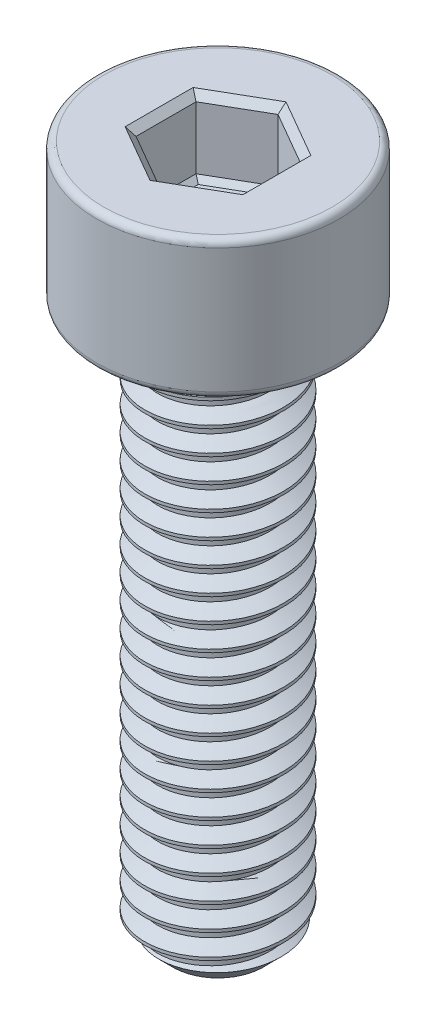
SolidWorks part; units mm, degrees
material "AISI Type A2 Tool Steel"
ref_plane "Front Plane" through (0, 0, 0) normal (0, 0, 1) x (1, 0, 0)
ref_plane "Top Plane" through (0, 0, 0) normal (0, 1, 0) x (1, 0, 0)
ref_plane "Right Plane" through (0, 0, 0) normal (1, 0, 0) x (0, 0, -1)
sketch "Sketch1" plane through (0, 0, 0) normal (0, 1, 0) x (1, 0, 0)
  circle A0 centre (0, 0) radius 2
  dimension "D1" = 4
extrude "Boss-Extrude1" add sketch "Sketch1" along normal blind 16
thread "Thread1" pitch 0.7 start angle 0, offset 1, length 0, pitch 0.7, diameter 4
ref_plane "Plane1" through (2, -1, 0) normal (0, 0, 1) x (1, 0, 0)
sketch "Thread Profile1" plane through (2, -1, 0) normal (0, 0, 1) x (1, 0, 0)
  line L0 (0, 0) -> (0, 0.7) construction
  line L11 (0, 0) -> (0, 0.6125)
  line L12 (0, 0.6125) -> (-0.3789, 0.3937)
  line L13 (-0.3789, 0.3937) -> (-0.3789, 0.2187)
  line L15 (-0.3789, 0.2187) -> (0, 0)
  line L17 (-0.3789, 0.3062) -> (0, 0.3062) construction
  point P2 (0, 0)
  dimension "Pitch" = 0.7
  dimension "Profile_Angle" = 60
  dimension "Profile_Land" = 0.175
  dimension "Profile_Height" = 0.3789
sketch "Sketch4" plane through (0, 16, 0) normal (0, -1, 0) x (-1, 0, 0)
  circle A0 centre (0, 0) radius 3.5
  dimension "D1" = 7
extrude "Boss-Extrude2" add sketch "Sketch4" against normal blind 4
fillet "Fillet1" radius 0.2 2 edges at (0, 16, -3.5) (0, 20, -3.5)
sketch "Sketch6" plane through (0, 0, 0) normal (0, 0, 1) x (1, 0, 0)
  line L0 (0, 0) -> (2.01, 0) construction
  line L1 (2.01, 0) -> (2.01, 0.7)
  line L2 (2.01, 0.7) -> (1.31, 0)
  line L3 (1.31, 0) -> (2.01, 0)
  line L4 (0, 0) -> (0, 0.3482) construction
  dimension "D1" = 0.7
  dimension "D2" = 45
  dimension "D3" = 2.01
revolve "Cut-Revolve1" cut sketch "Sketch6" angle 360 about L4
sketch "Sketch7" plane through (0, 20, 0) normal (0, 1, 0) x (1, 0, 0)
  line L1 (0, 1.7321) -> (-1.5, 0.866)
  line L2 (-1.5, 0.866) -> (-1.5, -0.866)
  line L3 (-1.5, -0.866) -> (0, -1.7321)
  line L4 (0, -1.7321) -> (1.5, -0.866)
  line L5 (1.5, -0.866) -> (1.5, 0.866)
  line L6 (1.5, 0.866) -> (0, 1.7321)
  circle A0 centre (0, 0) radius 1.5 construction
  dimension "D1" = 3
extrude "Cut-Extrude1" cut sketch "Sketch7" against normal blind 2
chamfer "Chamfer1" distance 0.2 angle 45 6 edges at (-1.5, 20, 0) (-0.75, 20, 1.299) (0.75, 20, 1.299) (1.5, 20, 0) (0.75, 20, -1.299) (-0.75, 20, -1.299)
sketch "Sketch8" plane through (0, 18, 0) normal (0, 1, 0) x (1, 0, 0)
  line L1 (0, 1.7321) -> (-1.5, 0.866)
  line L2 (-1.5, 0.866) -> (-1.5, -0.866)
  line L3 (-1.5, -0.866) -> (0, -1.7321)
  line L4 (0, -1.7321) -> (1.5, -0.866)
  line L5 (1.5, -0.866) -> (1.5, 0.866)
  line L6 (1.5, 0.866) -> (0, 1.7321)
  circle A0 centre (0, 0) radius 1.5 construction
extrude "Cut-Extrude2" cut sketch "Sketch8" against normal blind 0.15 draft 45
